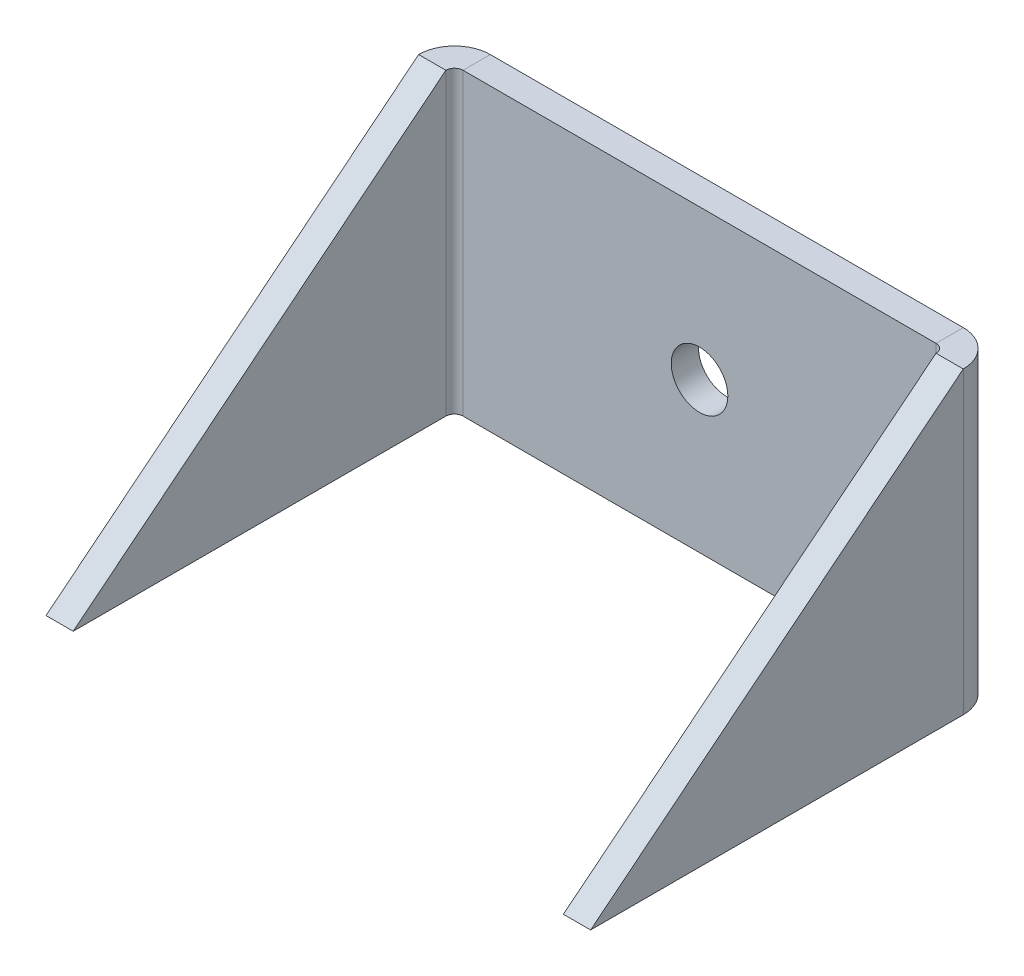
SolidWorks part; units mm, degrees
note: The reader was unsure of these and kept them because the rebuilt part matched: flange length of "Edge-Flange1".
material "6061-T6 (SS)"
ref_plane "X-Y Datum" through (0, 0, 0) normal (0, 0, 1) x (1, 0, 0)
ref_plane "X-Z Datum" through (0, 0, 0) normal (0, 1, 0) x (1, 0, 0)
ref_plane "Y-Z Datum" through (0, 0, 0) normal (1, 0, 0) x (0, 0, -1)
sketch "Sketch2" plane through (0, 0, 0) normal (0, 0, 1) x (1, 0, 0)
  line L1 (-28.575, 17.4625) -> (28.575, 17.4625)
  line L2 (-28.575, 17.4625) -> (-28.575, -17.4625)
  line L3 (-28.575, -17.4625) -> (28.575, -17.4625)
  line L4 (28.575, 17.4625) -> (28.575, -17.4625)
  line L5 (-28.575, 17.4625) -> (28.575, -17.4625) construction
  line L6 (-28.575, -17.4625) -> (28.575, 17.4625) construction
  circle A0 centre (0, 0) radius 3 construction
  point P0 (0, 0)
  dimension "D3" = 6
  dimension "D1" = 34.925
  dimension "D2" = 57.15
base flange "Base-Flange1" sketch "Sketch2" thickness 3.175 reverse thickness direction yes parameters "D1"=1
edge flange "Edge-Flange1" sketch "Sketch9" flange angle 90 flange length 47.625 flange position material outside bend radius 1 thickness 3.175 relief rectangular parameters "D6"=10
sketch "Sketch9" plane through (28.575, 0, 3.175) normal (1, 0, 0) x (0, 1, 0)
  line L2 (-17.4625, 0) -> (-17.4625, 44.45)
  line L3 (-17.4625, 44.45) -> (17.4625, 44.45)
  line L4 (17.4625, 44.45) -> (17.4625, 0)
  line L7 (-17.4625, 0) -> (17.4625, 0) construction
  line L8 (-17.4625, 0) -> (17.4625, 0)
bend "EdgeBend1" bend radius 1 bend angle 90 parameters "D5"=1
sketch "Sketch10" plane through (31.75, 0, 0) normal (1, 0, 0) x (0, 0, -1)
  line L0 (-4.175, 17.4625) -> (-47.625, -17.4625)
  line L1 (-47.625, 17.4625) -> (-47.625, -17.4625) construction
  line L3 (-47.625, -17.4625) -> (-4.175, -17.4625) construction
  line L7 (-4.175, -17.4625) -> (-4.175, 17.4625)
  line L8 (-4.175, 17.4625) -> (-47.625, 17.4625)
  line L9 (-47.625, 17.4625) -> (-47.625, -17.4625)
  line L10 (-47.625, -17.4625) -> (-4.175, -17.4625)
  line L12 (-4.175, 17.4625) -> (-47.625, 17.4625)
  line L13 (-47.625, 17.4625) -> (-47.625, -17.4625)
  dimension "D1" = 0
extrude "Cut-Extrude1" cut sketch "Sketch10" against normal blind 3.175 normal cut yes
mirror "Mirror1" about plane through (0, 0, 0) normal (1, 0, 0) of "Cut-Extrude1", "Edge-Flange1"
bend "MirrorBend1" bend radius 1 bend angle 90 parameters "D5"=2
sketch "Sketch11" [suppressed] plane through (32.75, 0, 0) normal (1, 0, 0) x (0, 0, -1)
  line L0 (-4.175, -15.875) -> (-44.45, 15.875)
extrude "Cut-Extrude2" [suppressed] cut sketch "Sketch11" against normal blind 3.175 and the other way through all
hole_wizard "M6 Clearance Hole1" positions "Sketch13" profile "Sketch14" hole size "M6" standard "ANSI Metric" end condition through all
sketch "Sketch13" plane through (0, 0, 3.175) normal (0, 0, 1) x (1, 0, 0)
  point P0 (0, 0)
sketch "Sketch14" plane through (0, 0, 3.175) normal (1, 0, 0) x (0, -1, 0)
  line L0 (0, 0) -> (0, 3.175)
  line L1 (0, 3.175) -> (3.3, 3.175)
  line L2 (3.3, 3.175) -> (3.3, 0)
  line L5 (3.3, 0) -> (0, 0)
  line L11 (0, -6.35) -> (0, 107.95) construction
  dimension "Thru Hole Dia." = 6.6
  dimension "Thru Hole Depth" = 3.175
sketch "Bend-Lines1" [suppressed] plane through (0, 0, 0) normal (0, 1, 0) x (1, 0, 0)
sketch "Bounding-Box1" [suppressed] plane through (0, 0, 0) normal (0, 1, 0) x (1, 0, 0)
sheet metal parameters "Sheet-Metal1" thickness 3.175 parameters "D1"=1
flat pattern "Flat-Pattern1" [suppressed]
sketch "Bend-Lines2" plane through (0, 0, 0) normal (0, 1, 0) x (1, 0, 0)
sketch3d "Bounding-Box2" [suppressed]
  line L0 (-63.5, -15.875, 0) -> (63.5, -15.875, 0) construction
  line L1 (-63.5, 15.875, 0) -> (63.5, 15.875, 0) construction
  line L2 (-63.5, -15.875, 0) -> (-63.5, 15.875, 0) construction
  line L3 (63.5, -15.875, 0) -> (63.5, 15.875, 0) construction
sheet metal parameters "Sheet-Metal2" thickness 3.175 parameters "D1"=1
flat pattern "Flat-Pattern1"
sketch "Bend-Lines2" plane through (0, 0, 0) normal (0, 0, -1) x (-1, 0, 0)
  line L0 (-30.6072, 15.875) -> (-30.6072, -15.875) construction
  line L1 (-30.6072, 15.875) -> (-30.6072, -15.875) construction
sketch3d "Bounding-Box2" [suppressed]
  line L0 (28.575, -15.875, 0) -> (-72.9144, -15.875, 0) construction
  line L1 (28.575, 15.875, 0) -> (-72.9144, 15.875, 0) construction
  line L2 (28.575, -15.875, 0) -> (28.575, 15.875, 0) construction
  line L3 (-72.9144, -15.875, 0) -> (-72.9144, 15.875, 0) construction
bend of the flat pattern "Flatten-<EdgeBend1>1"
sheet metal parameters "Sheet-Metal5" thickness 3.175 parameters "D1"=1
flat pattern "Flat-Pattern1"
sketch "Bend-Lines2" plane through (0, 0, 0) normal (0, 0, -1) x (-1, 0, 0)
  line L0 (-29.6072, 15.875) -> (-29.6072, -15.875) construction
  line L1 (-29.6072, 15.875) -> (-29.6072, -15.875) construction
  line L2 (29.6072, -15.875) -> (29.6072, 15.875) construction
  line L3 (29.6072, -15.875) -> (29.6072, 15.875) construction
sketch3d "Bounding-Box2" [suppressed]
  line L0 (71.9144, -15.875, 0) -> (-71.9144, -15.875, 0) construction
  line L1 (71.9144, 15.875, 0) -> (-71.9144, 15.875, 0) construction
  line L2 (71.9144, -15.875, 0) -> (71.9144, 15.875, 0) construction
  line L3 (-71.9144, -15.875, 0) -> (-71.9144, 15.875, 0) construction
bend of the flat pattern "Flatten-<EdgeBend1>1"
bend of the flat pattern "Flatten-<MirrorBend1>1"
sheet metal parameters "Sheet-Metal7" thickness 3.175 parameters "D1"=1
flat pattern "Flat-Pattern1"
sketch "Bend-Lines2" plane through (0, 0, 0) normal (0, 0, -1) x (-1, 0, 0)
  line L0 (-30.6072, 15.875) -> (-30.6072, -15.875) construction
  line L1 (-30.6072, 15.875) -> (-30.6072, -15.875) construction
sketch3d "Bounding-Box2" [suppressed]
  line L0 (28.575, -15.875, 0) -> (-72.9144, -15.875, 0) construction
  line L1 (28.575, 15.875, 0) -> (-72.9144, 15.875, 0) construction
  line L2 (28.575, -15.875, 0) -> (28.575, 15.875, 0) construction
  line L3 (-72.9144, -15.875, 0) -> (-72.9144, 15.875, 0) construction
bend of the flat pattern "Flatten-<EdgeBend1>1"
sheet metal parameters "Sheet-Metal8" thickness 3.175 parameters "D1"=1
flat pattern "Flat-Pattern1"
sketch "Bend-Lines2" plane through (0, 0, 0) normal (0, 0, -1) x (-1, 0, 0)
  line L0 (-30.6072, 15.875) -> (-30.6072, -15.875) construction
  line L1 (-30.6072, 15.875) -> (-30.6072, -15.875) construction
sketch3d "Bounding-Box2" [suppressed]
  line L0 (28.575, -15.875, 0) -> (-72.9144, -15.875, 0) construction
  line L1 (28.575, 15.875, 0) -> (-72.9144, 15.875, 0) construction
  line L2 (28.575, -15.875, 0) -> (28.575, 15.875, 0) construction
  line L3 (-72.9144, -15.875, 0) -> (-72.9144, 15.875, 0) construction
bend of the flat pattern "Flatten-<EdgeBend1>1"
sheet metal parameters "Sheet-Metal9" thickness 3.175 parameters "D1"=1
flat pattern "Flat-Pattern1"
sketch "Bend-Lines2" plane through (0, 0, 0) normal (0, 0, -1) x (-1, 0, 0)
  line L0 (-29.6072, 17.4625) -> (-29.6072, -17.4625) construction
  line L1 (-29.6072, 17.4625) -> (-29.6072, -17.4625) construction
  line L2 (29.6072, -17.4625) -> (29.6072, 17.4625) construction
  line L3 (29.6072, -17.4625) -> (29.6072, 17.4625) construction
sketch3d "Bounding-Box2" [suppressed]
  line L0 (75.0894, -17.4625, 0) -> (-75.0894, -17.4625, 0) construction
  line L1 (75.0894, 17.4625, 0) -> (-75.0894, 17.4625, 0) construction
  line L2 (75.0894, -17.4625, 0) -> (75.0894, 17.4625, 0) construction
  line L3 (-75.0894, -17.4625, 0) -> (-75.0894, 17.4625, 0) construction
bend of the flat pattern "Flatten-<EdgeBend1>1"
bend of the flat pattern "Flatten-<MirrorBend1>1"
